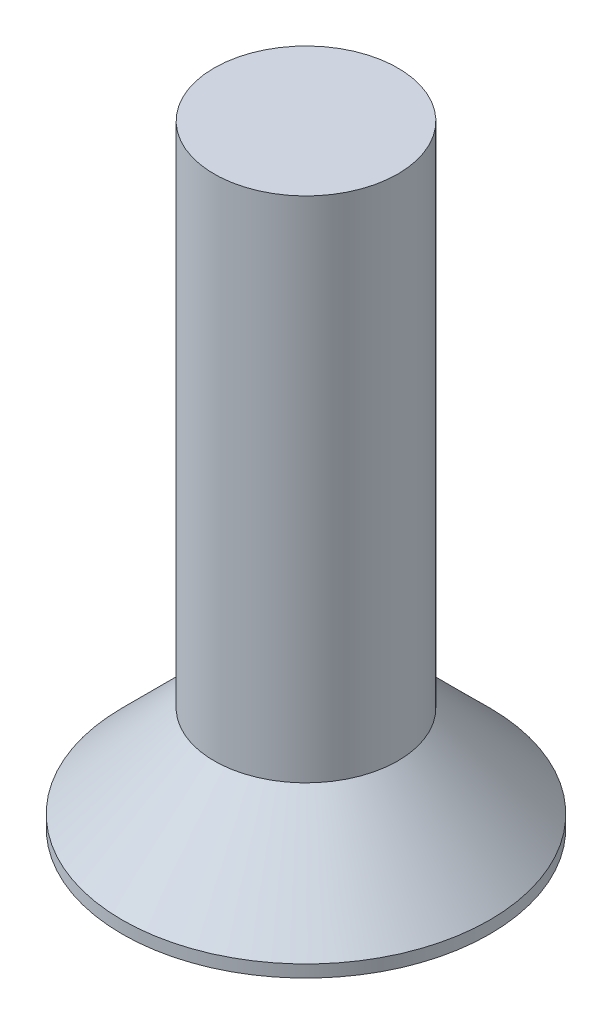
SolidWorks part; units mm, degrees
ref_plane "Front Plane" through (0, 0, 0) normal (0, 0, 1) x (1, 0, 0)
ref_plane "Top Plane" through (0, 0, 0) normal (0, 1, 0) x (1, 0, 0)
ref_plane "Right Plane" through (0, 0, 0) normal (1, 0, 0) x (0, 0, -1)
sketch "Sketch2" plane through (0, 0, 0) normal (0, 0, 1) x (1, 0, 0)
  line L1 (3, 0) -> (1.5, 1.5)
  line L2 (1.5, 1.5) -> (1.5, 9.8)
  line L3 (1.5, 9.8) -> (-1.5, 9.8)
  line L4 (-1.5, 9.8) -> (-1.5, 1.5)
  line L5 (-1.5, 1.5) -> (-3, 0)
  line L6 (0, 1.5) -> (0, 9.8)
  line L7 (1.5, 1.5) -> (-1.5, 1.5) construction
  line L8 (-3, 0) -> (-3, -0.2)
  line L9 (-3, -0.2) -> (3, -0.2)
  line L10 (3, -0.2) -> (3, 0)
  line L11 (0, 1.5) -> (0, -0.2)
  dimension "D1" = 45
  dimension "D2" = 45
  dimension "D3" = 6
  dimension "D4" = 3
  dimension "D5" = 1.7
  dimension "D6" = 10
revolve "Revolve1" add sketch "Sketch2" angle 360 about L6 region at (1.217, 0.5509, 0) region at (0.75, 5.65, 0)
sketch "Sketch3" plane through (0, -0.2, 0) normal (0, -1, 0) x (1, 0, 0)
  line L1 (0, 1.1547) -> (-1, 0.5774)
  line L2 (-1, 0.5774) -> (-1, -0.5774)
  line L3 (-1, -0.5774) -> (0, -1.1547)
  line L4 (0, -1.1547) -> (1, -0.5774)
  line L5 (1, -0.5774) -> (1, 0.5774)
  line L6 (1, 0.5774) -> (0, 1.1547)
  circle A0 centre (0, 0) radius 1 construction
  dimension "D1" = 2
extrude "Cut-Extrude1" cut sketch "Sketch3" against normal blind 1.5 and the other way through all
